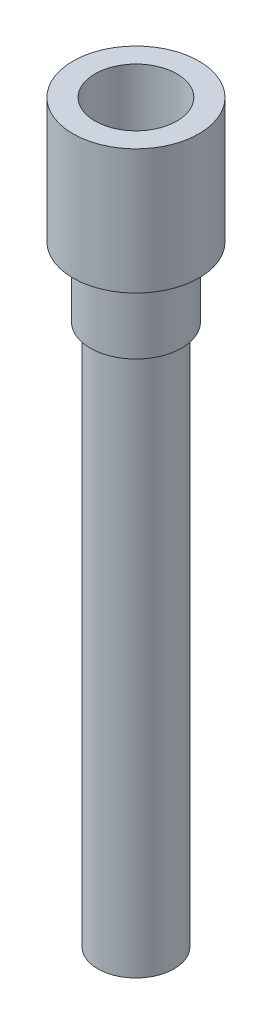
SolidWorks part; units mm, degrees
material "1023 Carbon Steel Sheet (SS)"
ref_plane "Front Plane" through (0, 0, 0) normal (0, 0, 1) x (1, 0, 0)
ref_plane "Top Plane" through (0, 0, 0) normal (0, 1, 0) x (1, 0, 0)
ref_plane "Right Plane" through (0, 0, 0) normal (1, 0, 0) x (0, 0, -1)
sketch "Sketch1" plane through (0, 0, 0) normal (0, 1, 0) x (1, 0, 0)
  circle A0 centre (0, 0) radius 2.58
  circle A1 centre (0, 0) radius 5.5
  circle A2 centre (0, 0) radius 4.58 construction
  dimension "D1" = 2
  dimension "D2" = 11
  dimension "D3" = 5.16
  dimension "D4" = 9.16
extrude "Boss-Extrude1" add sketch "Sketch1" along normal blind 78
sketch "Sketch2" plane through (0, 0, 0) normal (0, -1, 0) x (1, 0, 0)
  circle A0 centre (0, 0) radius 5.5
  circle A1 centre (0, 0) radius 5.5 construction
  circle A2 centre (0, 0) radius 5.5
  dimension "D1" = 11
sketch "Sketch4" plane through (0, 78, 0) normal (0, 1, 0) x (1, 0, 0)
  circle A0 centre (0, 0) radius 3.4
  circle A2 centre (0, 0) radius 5.5 construction
  dimension "D1" = 6.8
  dimension "D2" = 2.1
sketch "Sketch5" plane through (0, 78, 0) normal (0, 1, 0) x (1, 0, 0)
  circle A0 centre (0, 0) radius 6.5785
  circle M3 centre (0, 0) radius 5.5
  circle M4 centre (0, 0) radius 2.58
  dimension "D1" = 13.157
extrude "Boss-Extrude2" add sketch "Sketch5" along normal blind 10 contours M3 | A0 M3 | M4 region at (-6.3924, 78, 0) region at (-5.3444, 78, 0) region at (0, 78, 0)
sketch "Sketch6" plane through (0, 88, 0) normal (0, 1, 0) x (1, 0, 0)
  circle A0 centre (0, 0) radius 9.0785
  circle M9 centre (0, 0) radius 6.5785
  dimension "D1" = 18.157
extrude "Boss-Extrude3" add sketch "Sketch6" along normal blind 18 contours A0 | M9 region at (-8.8217, 88, 0) region at (0, 88, 0)
hole_wizard "G1/4 Tapped Hole2" positions "Sketch10" profile "Sketch11" tap size "G1/4" standard "ISO"
sketch "Sketch10" plane through (0, 106, 0) normal (0, 1, 0) x (1, 0, 0)
  point P0 (0, 0)
sketch "Sketch11" plane through (0, 106, 0) normal (1, 0, 0) x (0, 0, 1)
  line L0 (0, 0) -> (0, 18.5451)
  line L1 (0, 18.5451) -> (5.9, 15)
  line L2 (5.9, 15) -> (5.9, 0)
  line L5 (5.9, 0) -> (0, 0)
  line L10 (0, 18.5451) -> (-5.9, 15) construction
  line L11 (0, -6.35) -> (0, 107.95) construction
  dimension "Tap Drill Dia." = 11.8
  dimension "Tap Drill Depth" = 15
  dimension "Drill Angle" = 118
cosmetic thread "Hole Thread1" parameters "D1"=15, "D2"=13.157
ref_plane "Plane1" through (0, 94, 0) normal (0, -1, 0) x (-1, 0, 0)
sketch "Sketch15" plane through (0, 94, 0) normal (0, -1, 0) x (-1, 0, 0)
  circle A0 centre (0, 0) radius 2.5
  dimension "D1" = 5
extrude "Boss-Extrude4" add sketch "Sketch15" along normal up to surface (16 mm away) contours A0 region at (0, 94, 0) up to face at (0, 78, 2.58)
hole_wizard "M8 Tapped Hole1" positions "Sketch16" profile "Sketch17" tap size "M8" standard "ISO"
sketch "Sketch16" plane through (0, 94, 0) normal (0, 1, 0) x (1, 0, 0)
  point P0 (0, 0)
sketch "Sketch17" plane through (0, 94, 0) normal (1, 0, 0) x (0, 0, 1)
  line L0 (0, 0) -> (0, 87.0429)
  line L1 (0, 87.0429) -> (3.4, 85)
  line L2 (3.4, 85) -> (3.4, 0)
  line L5 (3.4, 0) -> (0, 0)
  line L10 (0, 87.0429) -> (-3.4, 85) construction
  line L11 (0, -6.35) -> (0, 107.95) construction
  dimension "Tap Drill Dia." = 6.8
  dimension "Tap Drill Depth" = 85
  dimension "Drill Angle" = 118
cosmetic thread "Hole Thread2" parameters "D1"=10, "D2"=8
equation "\"D1@Sketch6\"=13.157+2.5*2"
